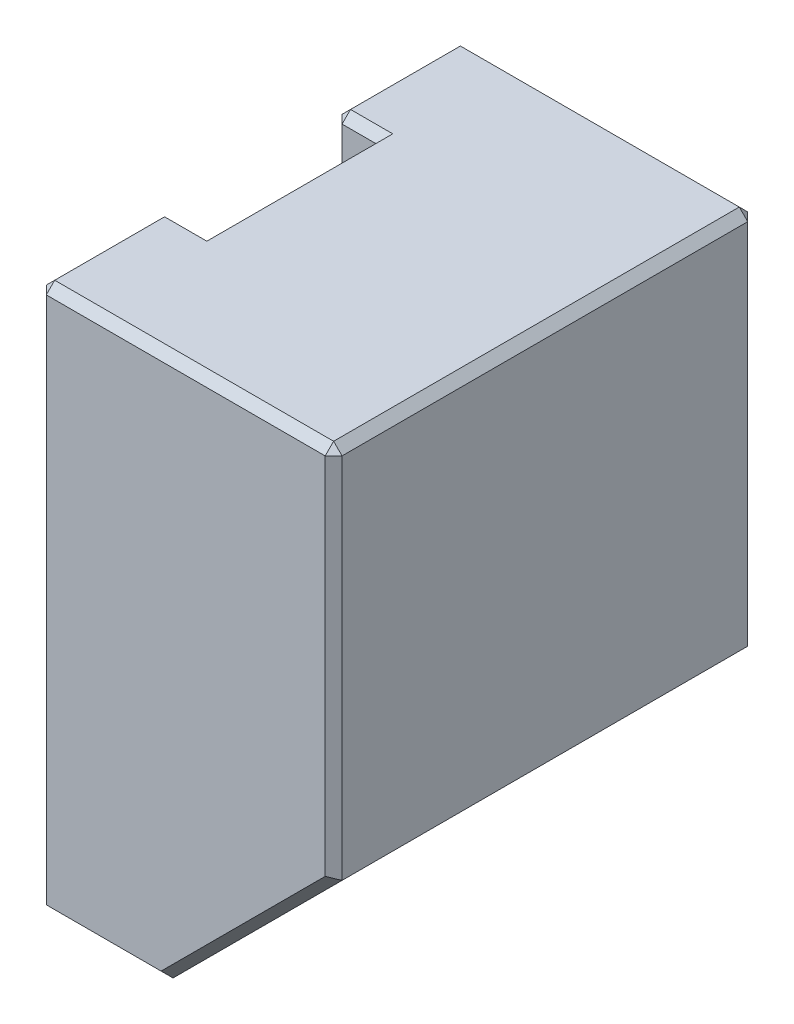
SolidWorks part; units mm, degrees
material "K110"
ref_plane "Front Plane" through (0, 0, 0) normal (0, 0, 1) x (1, 0, 0)
ref_plane "Top Plane" through (0, 0, 0) normal (0, 1, 0) x (1, 0, 0)
ref_plane "Right Plane" through (0, 0, 0) normal (1, 0, 0) x (0, 0, -1)
sketch "Sketch1" plane through (0, 0, 0) normal (0, 1, 0) x (1, 0, 0)
  line L1 (-17.5, -25) -> (17.5, -25)
  line L2 (-17.5, -25) -> (-17.5, 25)
  line L3 (-17.5, 25) -> (17.5, 25)
  line L4 (17.5, -25) -> (17.5, 25)
  line L5 (-17.5, -25) -> (17.5, 25) construction
  line L6 (-17.5, 25) -> (17.5, -25) construction
  point P0 (0, 0)
  dimension "D1" = 50
  dimension "D2" = 35
extrude "Boss-Extrude1" add sketch "Sketch1" against normal blind 64.5
sketch "Sketch2" plane through (0, 0, 25) normal (0, 0, 1) x (1, 0, 0)
  line L0 (-2.5, -64.5) -> (17.5, -44.5)
  line L1 (-17.5, -64.5) -> (17.5, -64.5) construction
  line L2 (17.5, -64.5) -> (17.5, 0) construction
  line L3 (17.5, -44.5) -> (17.5, -64.5)
  line L4 (17.5, -64.5) -> (-2.5, -64.5)
  dimension "D1" = 20
  dimension "D2" = 45
extrude "Cut-Extrude1" cut sketch "Sketch2" against normal up to next
sketch "Sketch3" plane through (-17.5, 0, 0) normal (-1, 0, 0) x (0, 0, 1)
  line L0 (-25, -64.5) -> (25, -64.5) construction
  line L1 (-7, -64.5) -> (7, -64.5)
  line L2 (-7, -64.5) -> (-7, -44.5)
  line L3 (-7, -44.5) -> (7, -44.5)
  line L4 (7, -64.5) -> (7, -44.5)
  line L5 (-25, -44.5) -> (25, -44.5) construction
  point P8 (0, -44.5)
  dimension "D1" = 14
  dimension "D2" = 20
extrude "Cut-Extrude2" cut sketch "Sketch3" against normal up to next
fillet "Fillet1" 2 edges at (0, -44.5, -7) (0, -44.5, 7) type full round first side face at (-5, -54.5, -7) second side face at (-5, -54.5, 7) middle face at (0, -44.5, 0)
sketch "Sketch4" plane through (0, 0, 0) normal (0, 1, 0) x (1, 0, 0)
  line L0 (-17.5, 0) -> (17.5, 0) construction
  line L1 (-17.5, 25) -> (-17.5, -25) construction
  line L2 (17.5, -25) -> (17.5, 25) construction
  line L4 (-17.5, -10) -> (-12.5, -10)
  line L5 (-17.5, -10) -> (-17.5, 10)
  line L6 (-17.5, 10) -> (-12.5, 10)
  line L7 (-12.5, -10) -> (-12.5, 10)
  dimension "D1" = 5
  dimension "D2" = 20
extrude "Cut-Extrude3" cut sketch "Sketch4" against normal blind 43
sketch "Sketch5" plane through (-17.5, 0, 0) normal (-1, 0, 0) x (0, 0, 1)
  line L0 (-10, -43) -> (-10, 0) construction
  line L1 (-15, -43) -> (15, -43)
  line L2 (-15, -43) -> (-15, -38)
  line L3 (-15, -38) -> (15, -38)
  line L4 (15, -43) -> (15, -38)
  line L5 (-10, -43) -> (10, -43) construction
  line L6 (10, -43) -> (10, 0) construction
  dimension "D1" = 5
  dimension "D2" = 5
  dimension "D3" = 5
extrude "Cut-Extrude4" cut sketch "Sketch5" against normal up to surface (5 mm away) up to face at (-12.5, -21.5, 0)
fillet "Fillet5" 2 edges at (-15, -43, -15) (-15, -38, -15) type full round first side face at (-15, -43, 0) second side face at (-15, -38, -12.5) middle face at (-15, -40.5, -15)
fillet "Fillet6" 2 edges at (-15, -43, 15) (-15, -38, 15) type full round first side face at (-15, -43, 1.25) second side face at (-15, -38, 12.5) middle face at (-15, -40.5, 15)
chamfer "Chamfer1" distance 1 angle 45 28 edges at (-17.5, -38, 11.25) (-17.5, -19, 10) (-17.5, -64.5, 16) (-17.5, -58, 7) (-17.5, -44.5, 0) (-17.5, -58, -7) (-17.5, -64.5, -16) (-17.5, -40.5, 15) (-17.5, -43, 0) (-17.5, -40.5, -15) (-17.5, -38, -11.25) (-17.5, -19, -10) (17.5, 0, 0) (17.5, -22.25, -25) (0, 0, -25) (7.5, -54.5, -25) (-10, -64.5, -25) (-17.5, -32.25, -25) (-17.5, 0, -17.5) (-15, 0, -10) (-12.5, 0, 0) (-15, 0, 10) (-17.5, 0, 17.5) (-10, -64.5, 25) (-17.5, -32.25, 25) (0, 0, 25) (17.5, -22.25, 25) (7.5, -54.5, 25)
